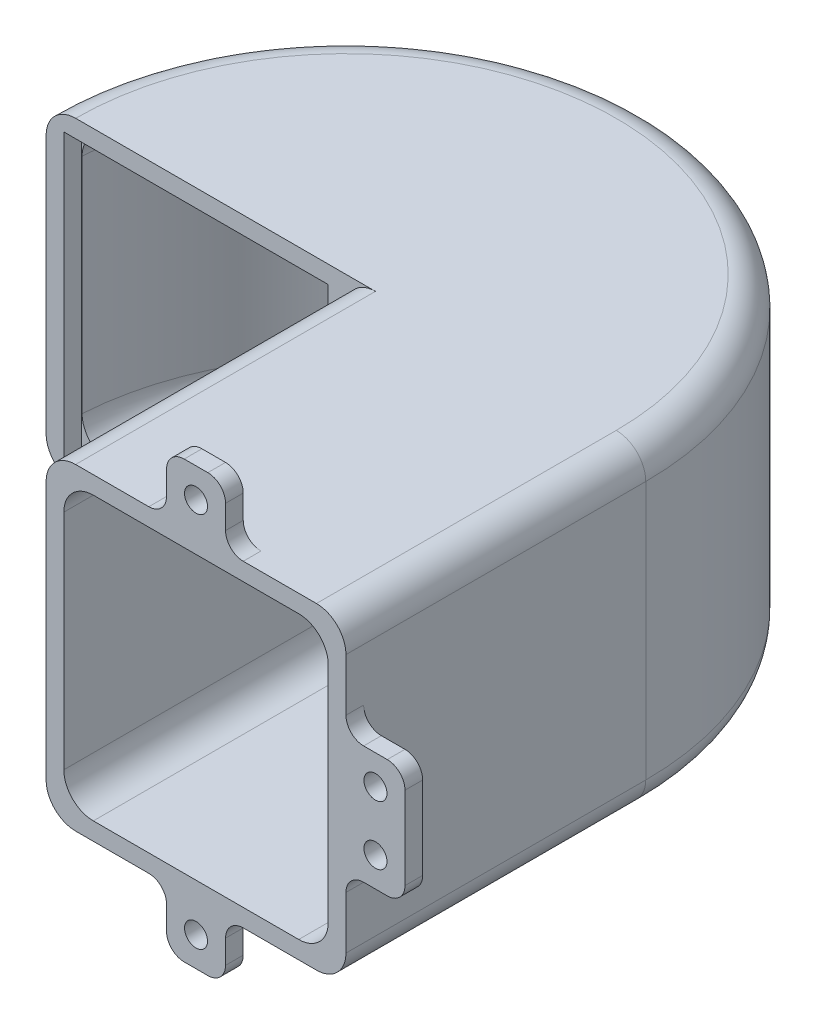
SolidWorks part; units mm, degrees
ref_plane "Front Plane" through (0, 0, 0) normal (0, 0, 1) x (1, 0, 0)
ref_plane "Top Plane" through (0, 0, 0) normal (0, 1, 0) x (1, 0, 0)
ref_plane "Right Plane" through (0, 0, 0) normal (1, 0, 0) x (0, 0, -1)
sketch "Sketch1" plane through (0, 0, 0) normal (0, 1, 0) x (1, 0, 0)
  line L0 (0, 0) -> (0, 50.8)
  line L1 (0, 0) -> (50.8, 0)
  line L2 (50.8, 0) -> (50.8, 50.8)
  line L3 (0, 50.8) -> (-50.8, 50.8)
  arc A0 (50.8, 50.8) -> (-50.8, 50.8) centre (0, 50.8) ccw
  dimension "D1" = 50.8
  dimension "D3" = 50.8
extrude "Boss-Extrude1" add sketch "Sketch1" along normal blind 50.8
sketch "Sketch2" plane through (0, 50.8, 0) normal (0, 1, 0) x (1, 0, 0)
  line L12 (3, 3) -> (47.8, 3)
  line L13 (47.8, 3) -> (47.8, 50.8)
  line L14 (-47.7058, 53.8) -> (3, 53.8)
  line L15 (3, 53.8) -> (3, 3)
  line L16 (3, 3) -> (47.8, 3)
  line L17 (47.8, 3) -> (47.8, 50.8)
  line L18 (-47.7058, 53.8) -> (3, 53.8)
  line L19 (3, 53.8) -> (3, 3)
  arc A3 (47.8, 50.8) -> (-47.7058, 53.8) centre (0, 50.8) ccw
  arc A4 (47.8, 50.8) -> (-47.7058, 53.8) centre (0, 50.8) ccw
  dimension "D1" = 3
extrude "Cut-Extrude1" cut sketch "Sketch2" against normal offset from surface (47.8 mm away) 3 up to face at (10.16, 0, -40.64)
sketch "Sketch3" plane through (0, 50.8, 0) normal (0, 1, 0) x (1, 0, 0)
  line L0 (0, 50.8) -> (0, 0)
  line L1 (0, 0) -> (50.8, 0)
  line L2 (50.8, 0) -> (50.8, 50.8)
  line L3 (0, 50.8) -> (-50.8, 50.8)
  arc A0 (-50.8, 50.8) -> (50.8, 50.8) centre (0, 50.8) cw
extrude "Boss-Extrude2" add sketch "Sketch3" along normal blind 3
sketch "Sketch4" plane through (0, 0, 0) normal (0, 0, 1) x (1, 0, 0)
  line L14 (3, 3) -> (47.8, 3)
  line L15 (47.8, 3) -> (47.8, 50.8)
  line L16 (47.8, 50.8) -> (3, 50.8)
  line L17 (3, 50.8) -> (3, 3)
  line L18 (3, 3) -> (47.8, 3)
  line L19 (47.8, 3) -> (47.8, 50.8)
  line L20 (47.8, 50.8) -> (3, 50.8)
  line L21 (3, 50.8) -> (3, 3)
  dimension "D1" = 3
extrude "Cut-Extrude2" cut sketch "Sketch4" against normal blind 3
sketch "Sketch5" plane through (0, 0, -50.8) normal (0, 0, 1) x (1, 0, 0)
  line L8 (-47.8, 3) -> (-3, 3)
  line L9 (-3, 3) -> (-3, 50.8)
  line L10 (-3, 50.8) -> (-47.8, 50.8)
  line L11 (-47.8, 50.8) -> (-47.8, 3)
  line L12 (-47.8, 3) -> (-3, 3)
  line L13 (-3, 3) -> (-3, 50.8)
  line L14 (-3, 50.8) -> (-47.8, 50.8)
  line L15 (-47.8, 50.8) -> (-47.8, 3)
  dimension "D1" = 3
extrude "Cut-Extrude3" cut sketch "Sketch5" against normal blind 3
sketch "Sketch6" plane through (0, 0, 0) normal (0, 0, 1) x (1, 0, 0)
  line L0 (0, 53.8) -> (50.8, 53.8) construction
  line L1 (20.4, 53.8) -> (30.4, 53.8)
  line L2 (20.4, 53.8) -> (20.4, 63.8)
  line L3 (20.4, 63.8) -> (30.4, 63.8)
  line L4 (30.4, 53.8) -> (30.4, 63.8)
  line L5 (50.8, 53.8) -> (50.8, 0) construction
  line L6 (50.8, 36.9) -> (60.8, 36.9)
  line L7 (50.8, 36.9) -> (50.8, 16.9)
  line L8 (50.8, 16.9) -> (60.8, 16.9)
  line L9 (60.8, 36.9) -> (60.8, 16.9)
  line L10 (0, 0) -> (50.8, 0) construction
  line L11 (30.4, 0) -> (20.4, 0)
  line L12 (30.4, 0) -> (30.4, -10)
  line L13 (30.4, -10) -> (20.4, -10)
  line L14 (20.4, 0) -> (20.4, -10)
  point P18 (9.3396, 0)
  point P19 (25.4, 0)
  point P20 (25.4, 0)
  point P21 (60.8, 20.3739)
  point P22 (60.8, 27.6827)
  point P23 (50.8, 26.9)
  point P24 (50.8, 26.9)
  dimension "D1" = 10
  dimension "D2" = 10
  dimension "D3" = 20
extrude "Boss-Extrude3" add sketch "Sketch6" against normal blind 3
fillet "Fillet1" radius 5 12 edges at (0, 53.8, -101.6) (0, 0, -101.6) (50.8, 53.8, -25.4) (50.8, 0, -25.4) (1.5007, 3, -98.5764) (1.5007, 50.8, -98.5764) (47.8, 3, -25.4) (47.8, 50.8, -25.4) (3, 50.8, -26.9) (3, 3, -26.9) (0, 53.8, -25.4) (0, 0, -25.4)
fillet "Fillet2" radius 3 12 edges at (60.8, 16.9, -1.5) (50.8, 16.9, -1.5) (60.8, 36.9, -1.5) (50.8, 36.9, -1.5) (20.4, 53.8, -1.5) (20.4, 63.8, -1.5) (30.4, 63.8, -1.5) (30.4, 53.8, -1.5) (20.4, -10, -1.5) (20.4, 0, -1.5) (30.4, -10, -1.5) (30.4, 0, -1.5)
hole_wizard "M3.5 Clearance Hole2" positions "Sketch7" profile "Sketch8" hole size "M3.5" standard "ANSI Metric" end condition through all
sketch "Sketch7" plane through (0, 0, -3) normal (0, 0, -1) x (-1, 0, 0)
  line L0 (-55.8, 31.9) -> (-55.8, 21.9)
  line L2 (-55.8, 26.9) -> (-60.8, 26.9) construction
  line L3 (-60.8, 19.9) -> (-60.8, 33.9) construction
  line L5 (-27.4, 63.8) -> (-23.4, 63.8) construction
  line L6 (-20.4, 60.8) -> (-20.4, 56.8) construction
  line L7 (-20.4, -3) -> (-20.4, -7) construction
  line L8 (-23.4, -10) -> (-27.4, -10) construction
  point P1 (-55.8, 31.9)
  point P2 (-55.8, 21.9)
  point P11 (-25.4, 58.8)
  point P18 (-25.4, -5)
  dimension "D1" = 5
  dimension "D2" = 10
  dimension "D3" = 5
  dimension "D4" = 5
  dimension "D5" = 5
  dimension "D6" = 5
sketch "Sketch8" plane through (55.8, 31.9, -3) normal (1, 0, 0) x (0, 1, 0)
  line L0 (0, 0) -> (0, 3)
  line L1 (0, 3) -> (1.95, 3)
  line L2 (1.95, 3) -> (1.95, 0.025)
  line L3 (1.95, 0.025) -> (1.975, 0)
  line L5 (1.975, 0) -> (0, 0)
  line L6 (-1.95, 0.025) -> (-1.975, 0) construction
  line L11 (0, -6.35) -> (0, 107.95) construction
  dimension "Thru Hole Dia." = 3.9
  dimension "Thru Hole Depth" = 3
  dimension "Near C'Sink Dia." = 3.95
  dimension "Near C'Sink Angle" = 90
